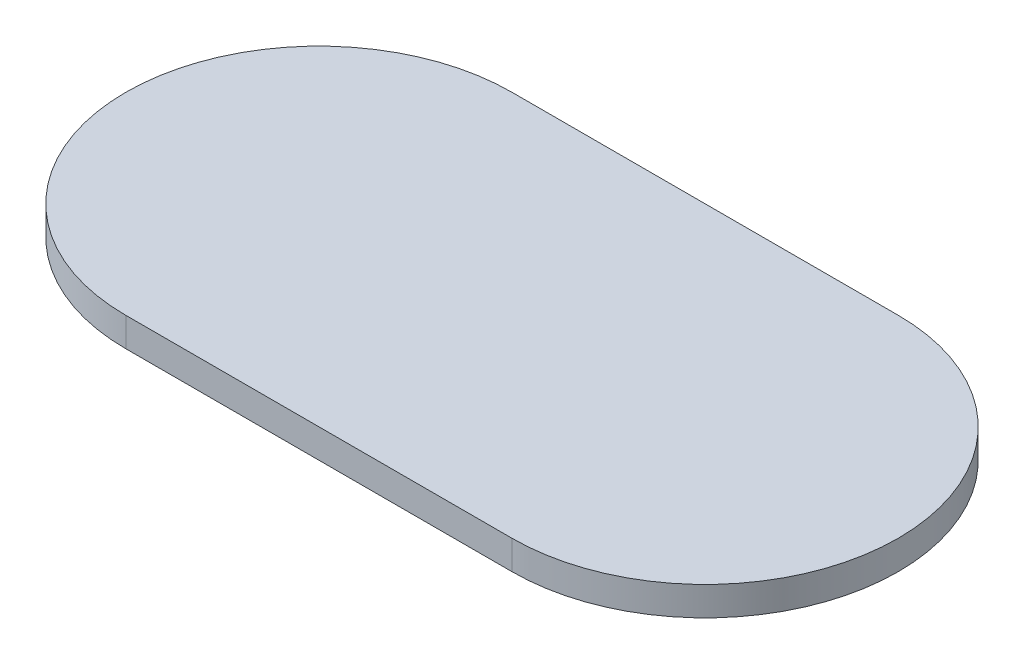
SolidWorks part; units mm, degrees
ref_plane "Front Plane" through (0, 0, 0) normal (0, 0, 1) x (1, 0, 0)
ref_plane "Top Plane" through (0, 0, 0) normal (0, 1, 0) x (1, 0, 0)
ref_plane "Right Plane" through (0, 0, 0) normal (1, 0, 0) x (0, 0, -1)
sketch "Sketch1" plane through (0, 0, 0) normal (0, 1, 0) x (1, 0, 0)
  line L1 (-25.4, -25.4) -> (25.4, -25.4)
  line L3 (-25.4, 25.4) -> (25.4, 25.4)
  line L5 (-25.4, -25.4) -> (25.4, 25.4) construction
  line L6 (-25.4, 25.4) -> (25.4, -25.4) construction
  arc A0 (-25.4, 25.4) -> (-25.4, -25.4) centre (-25.4, 0) ccw
  arc A1 (25.4, 25.4) -> (25.4, -25.4) centre (25.4, 0) cw
  point P0 (0, 0)
  point P8 (-50.8, 0)
  point P9 (50.8, 0)
  dimension "D1" = 50.8
  dimension "D2" = 101.6
extrude "Boss-Extrude1" add sketch "Sketch1" along normal blind 3.81
